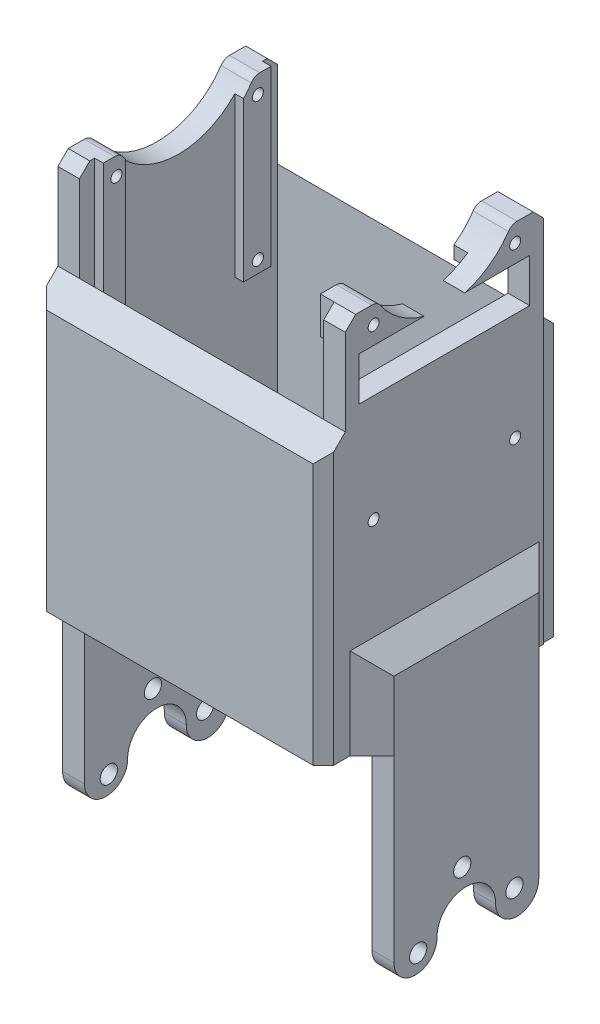
SolidWorks part; units mm, degrees
material "PLA"
ref_plane "Front Plane" through (0, 0, 0) normal (0, 0, 1) x (1, 0, 0)
ref_plane "Top Plane" through (0, 0, 0) normal (0, 1, 0) x (1, 0, 0)
ref_plane "Right Plane" through (0, 0, 0) normal (1, 0, 0) x (0, 0, -1)
sketch "Sketch1" plane through (0, 0, 0) normal (0, 0, 1) x (1, 0, 0)
  line L0 (0, 0) -> (35.4, 0)
  line L1 (35.4, 0) -> (35.4, 51.875)
  line L2 (0, 0) -> (-3.125, 0) construction
  line L3 (35.4, 0) -> (38.525, 0) construction
  line L4 (-3.125, -3.125) -> (38.525, -3.125)
  line L5 (38.525, -3.125) -> (38.525, 51.875)
  line L6 (-3.125, -3.125) -> (-3.125, 51.875)
  line L7 (0, 0) -> (0, 51.875)
  line L8 (0, 51.875) -> (-3.125, 51.875)
  line L9 (35.4, 51.875) -> (38.525, 51.875)
  dimension "D1" = 35.4
  dimension "D2" = 3.125
  dimension "D3" = 3.125
  dimension "D4" = 3.125
  dimension "D5" = 55
  dimension "D6" = 55
extrude "Boss-Extrude1" add sketch "Sketch1" along normal blind 28.72
sketch "Sketch2" plane through (38.525, 0, 0) normal (1, 0, 0) x (0, 0, -1)
  line L0 (-28.72, 46.285) -> (0, 46.285) construction
  line L1 (-28.72, -3.125) -> (-28.72, 51.875) construction
  line L2 (0, -3.125) -> (0, 51.875) construction
  line L3 (-28.72, 51.875) -> (0, 51.875) construction
  line L4 (-14.36, 46.285) -> (-14.36, 57.485) construction
  circle A0 centre (-14.36, 57.485) radius 11.2
  dimension "D1" = 5.59
  dimension "D2" = 11.2
extrude "Cut-Extrude1" cut sketch "Sketch2" against normal through all
fillet "Fillet2" radius 1.5 4 edges at (-1.5625, 51.875, 24.0537) (-1.5625, 51.875, 4.6663) (36.9625, 51.875, 4.6663) (36.9625, 51.875, 24.0537)
sketch "Sketch3" plane through (0, 0, 0) normal (0, 0, -1) x (-1, 0, 0)
  line L1 (-38.325, 37.875) -> (3.125, 37.875)
  line L2 (-38.325, 37.875) -> (-38.325, -3.125)
  line L3 (-38.325, -3.125) -> (3.125, -3.125)
  line L4 (3.125, 37.875) -> (3.125, -3.125)
extrude "Boss-Extrude2" add sketch "Sketch3" along normal blind 3.175
sketch "Sketch4" plane through (0, 0, 28.72) normal (0, 0, 1) x (1, 0, 0)
  line L1 (-3.125, 37.875) -> (38.525, 37.875)
  line L2 (-3.125, 37.875) -> (-3.125, -3.125)
  line L3 (-3.125, -3.125) -> (38.525, -3.125)
  line L4 (38.525, 37.875) -> (38.525, -3.125)
extrude "Boss-Extrude3" add sketch "Sketch4" along normal blind 3.175
chamfer "Chamfer1" distance 3.175 angle 45 2 edges at (17.6, 37.875, -3.175) (17.7, 37.875, 31.895)
chamfer "Chamfer2" distance 1.5 angle 45 4 edges at (-1.5625, 51.875, 0) (36.9625, 51.875, 0) (-1.5625, 51.875, 28.72) (36.9625, 51.875, 28.72)
chamfer "Chamfer3" distance 1.5 angle 45 4 edges at (-3.125, 15.7875, -3.175) (38.325, 15.7875, -3.175) (38.525, 15.7875, 31.895) (-3.125, 15.7875, 31.895)
sketch "Sketch5" plane through (0, 0, 0) normal (1, 0, 0) x (0, 0, -1)
  line L0 (-3.8368, 51.875) -> (-1.5, 51.875) construction
  line L2 (-2.2006, 51.875) -> (-2.2006, 26.7908)
  line L3 (-2.2006, 26.7908) -> (-6.2006, 26.7908)
  line L4 (-6.2006, 49.8127) -> (-6.2006, 26.7908)
  line L6 (-26.5194, 51.875) -> (-26.5194, 26.7908)
  line L7 (-26.5194, 26.7908) -> (-23.7797, 26.7908)
  line L8 (-23.7797, 51.4262) -> (-23.7797, 51.391)
  line L9 (-27.22, 51.875) -> (-24.8832, 51.875) construction
  line L10 (-3.8368, 51.875) -> (-2.2006, 51.875)
  line L11 (-26.5194, 51.875) -> (-24.8832, 51.875)
  line L12 (-23.7797, 26.7908) -> (-23.2826, 26.7908)
  line L13 (-23.2826, 26.7908) -> (-23.2826, 50.7154)
  circle A0 centre (-24.61, 49.2608) radius 0.8
  circle A1 centre (-24.61, 28.5608) radius 0.8
  circle A2 centre (-4.11, 28.5608) radius 0.8
  circle A3 centre (-4.11, 49.2608) radius 0.8
  arc A4 (-3.8368, 51.875) -> (-5.0797, 51.2148) centre (-3.8368, 50.375) ccw construction
  arc A5 (-23.6403, 51.2148) -> (-5.0797, 51.2148) centre (-14.36, 57.485) ccw construction
  arc A6 (-23.6403, 51.2148) -> (-24.8832, 51.875) centre (-24.8832, 50.375) ccw construction
  arc A7 (-3.8368, 51.875) -> (-5.0797, 51.2148) centre (-3.8368, 50.375) ccw
  arc A8 (-23.6403, 51.2148) -> (-23.7797, 51.4262) centre (-14.36, 57.485) ccw
  arc A9 (-23.6403, 51.2148) -> (-24.8832, 51.875) centre (-24.8832, 50.375) ccw
  arc A10 (-6.2006, 49.8127) -> (-5.0797, 51.2148) centre (-14.36, 57.485) ccw
  line M8 (-1.5, 51.875) -> (-3.8368, 51.875)
  arc M9 (-3.8368, 51.875) -> (-5.0797, 51.2148) centre (-3.8368, 50.375) ccw
  arc M10 (-5.0797, 51.2148) -> (-23.6403, 51.2148) centre (-14.36, 57.485) cw
  arc M11 (-23.6403, 51.2148) -> (-24.8832, 51.875) centre (-24.8832, 50.375) ccw
  line M12 (-24.8832, 51.875) -> (-27.22, 51.875)
extrude "Boss-Extrude4" add sketch "Sketch5" along normal blind 1.25 contours L4 L3 L2 A3 A2 M10 M8 M9 | L8 L6 L7 A1 A0 M11 M12 region at (0, 39.1233, 4.1775) region at (0, 39.2642, 24.9256)
sketch "Sketch6" plane through (0, 0, 0) normal (1, 0, 0) x (0, 0, -1)
  circle A0 centre (-24.61, 49.2608) radius 0.8
  circle A1 centre (-24.61, 28.5608) radius 0.8
  circle A2 centre (-4.11, 28.5608) radius 0.8
  circle A3 centre (-4.11, 49.2608) radius 0.8
extrude "Cut-Extrude2" cut sketch "Sketch6" against normal up to next
sketch "Sketch7" plane through (0, -3.125, 0) normal (0, -1, 0) x (1, 0, 0)
  line L0 (11.7, 22.36) -> (23.7, 22.36) construction
  line L1 (23.7, 22.36) -> (23.7, 6.36) construction
  line L2 (23.7, 6.36) -> (11.7, 6.36) construction
  line L3 (11.7, 6.36) -> (11.7, 22.36) construction
  line L6 (-3.125, 30.395) -> (-3.125, -1.675) construction
  line L7 (-1.625, 31.895) -> (37.025, 31.895) construction
  circle A0 centre (11.7, 22.36) radius 1.35
  circle A1 centre (23.7, 22.36) radius 1.35
  circle A2 centre (23.7, 6.36) radius 1.35
  circle A3 centre (11.7, 6.36) radius 1.35
  dimension "D1" = 2.7
  dimension "D2" = 2.7
  dimension "D3" = 2.7
  dimension "D4" = 2.7
  dimension "D5" = 14.825
  dimension "D6" = 9.535
extrude "Cut-Extrude3" cut sketch "Sketch7" against normal up to next
sketch "Sketch8" plane through (35.4, 0, 0) normal (-1, 0, 0) x (0, 0, 1)
  line L0 (7.86, 48.7133) -> (7.86, 45.9108) construction
  line L1 (1.5, 51.875) -> (5.0709, 51.875)
  line L2 (1.5, 51.875) -> (1.5, 46.5164)
  line L3 (1.5, 46.5164) -> (7.86, 46.5164)
  line L4 (7.86, 48.7133) -> (7.86, 46.5164)
  line L5 (20.86, 45.9108) -> (20.86, 48.7133) construction
  line L6 (20.86, 46.5164) -> (27.22, 46.5164)
  line L7 (20.86, 46.5164) -> (20.86, 48.7133)
  line L8 (23.6491, 51.875) -> (27.22, 51.875)
  line L9 (27.22, 46.5164) -> (27.22, 51.875)
  line L10 (28.72, 0) -> (28.72, 37.875) construction
  line L11 (28.72, 27.0608) -> (0, 27.0608)
  line L12 (28.72, 27.0608) -> (28.72, 22.5608)
  line L13 (28.72, 22.5608) -> (0, 22.5608)
  line L14 (0, 27.0608) -> (0, 22.5608)
  circle A0 centre (24.61, 49.2608) radius 0.8
  circle A1 centre (4.11, 49.2608) radius 0.8
  circle A2 centre (4.11, 24.8108) radius 0.8
  circle A3 centre (24.61, 24.735) radius 0.8758
  arc A4 (5.0077, 51.9796) -> (7.7768, 48.8846) centre (14.36, 57.5608) ccw construction
  arc A5 (5.0709, 51.875) -> (7.7768, 48.8846) centre (14.36, 57.5608) ccw
  arc A6 (20.9432, 48.8846) -> (23.7123, 51.9796) centre (14.36, 57.5608) ccw construction
  arc A7 (20.9432, 48.8846) -> (23.6491, 51.875) centre (14.36, 57.5608) ccw
  spline S0 degree 3 poles (-1990.0282, 140.523) (-63.2874, 38.9164) (7.1505, 51.8916) (8.5344, 45.7425) (-54.2619, 48.1267) (797.0615, -1788.4088) knots -94.086847 -94.086847 -94.086847 -94.086847 0.333333 0.666667 91.791331 91.791331 91.791331 91.791331 weights 1 1 1 1 1 1 only from (7.8374, 48.8108) to (7.86, 48.7133) construction
  spline S1 degree 3 poles (-490.8158, 1985.2839) (-30.2177, -10.261) (5.7924, 51.2853) (9.6673, 46.6143) (-37.1403, 7.4582) (460.9115, -1898.6662) knots -96.396237 -96.396237 -96.396237 -96.396237 0.333333 0.666667 89.616596 89.616596 89.616596 89.616596 weights 1 1 1 1 1 1 only from (7.7768, 48.8846) to (7.8374, 48.8108) construction
  spline S2 degree 3 poles (7.8374, 48.8108) (7.8425, 48.8003) (7.851, 48.7791) (7.8584, 48.746) (7.86, 48.7242) (7.86, 48.7133) knots 0 0 0 0 0.333333 0.666667 1 1 1 1 weights 1 1 1 1 1 1
  spline S3 degree 3 poles (7.7768, 48.8846) (7.785, 48.8784) (7.8005, 48.8647) (7.8213, 48.8396) (7.8325, 48.8208) (7.8374, 48.8108) knots 0 0 0 0 0.333333 0.666667 1 1 1 1 weights 1 1 1 1 1 1
  spline S4 degree 3 poles (356.7329, 2019.8863) (65.3071, 28.7044) (19.6993, 46.3936) (21.999, 51.095) (61.1419, 27.6757) (-1071.4379, -1626.044) knots -39.976297 -39.976297 -39.976297 -39.976297 0.341381 0.67758 38.768425 38.768425 38.768425 38.768425 weights 1 1 1 1 1 1 only from (20.86, 48.7133) to (20.9432, 48.8846) construction
  spline S5 degree 3 poles (20.86, 48.7133) (20.86, 48.7357) (20.8668, 48.7804) (20.896, 48.8401) (20.9264, 48.8718) (20.9432, 48.8846) knots 0 0 0 0 0.341381 0.67758 1 1 1 1 weights 1 1 1 1 1 1
  point P42 (0, 24.8108)
  line M9 (0, 37.875) -> (0, 0)
  line M11 (28.72, 0) -> (28.72, 37.875)
  line M14 (27.22, 51.875) -> (24.8832, 51.875)
  arc M15 (24.8832, 51.875) -> (23.6403, 51.2148) centre (24.8832, 50.375) ccw
  arc M16 (23.6403, 51.2148) -> (5.0797, 51.2148) centre (14.36, 57.485) cw
  arc M17 (5.0797, 51.2148) -> (3.8368, 51.875) centre (3.8368, 50.375) ccw
  line M18 (3.8368, 51.875) -> (1.5, 51.875)
  dimension "D1" = 4.5
extrude "Boss-Extrude5" add sketch "Sketch8" along normal blind 2 contours L6 L9 L7 A0 M14 M15 M16 | L4 L2 L3 A1 M16 M17 M18 | L13 L11 A3 A2 M11 M9 region at (35.4, 49.6068, 22.4374) region at (35.4, 51.7918, 2.6684) region at (35.4, 24.8122, 14.3273)
sketch "Sketch9" plane through (35.4, 0, 0) normal (-1, 0, 0) x (0, 0, 1)
  line L0 (24.61, 50.0607) -> (24.61, 48.4608) construction
  line L1 (4.11, 50.0607) -> (4.11, 48.4608) construction
  line L2 (4.11, 25.6107) -> (4.11, 24.0108) construction
  line L3 (24.61, 25.6107) -> (24.61, 24.0108) construction
  line L4 (26.72, 24.4506) -> (26.72, 51.0993) construction
  line L5 (26.72, 46.6769) -> (2, 46.6769)
  line L6 (26.72, 46.6769) -> (26.72, 40.3691)
  line L7 (26.72, 40.3691) -> (2, 40.3691)
  line L8 (2, 46.6769) -> (2, 40.3691)
  line L9 (2, 51.0993) -> (2, 24.4506) construction
  circle A0 centre (24.61, 24.8107) radius 0.8
  circle A1 centre (4.11, 24.8107) radius 0.8
  circle A2 centre (4.11, 49.2607) radius 0.8
  circle A3 centre (24.61, 49.2607) radius 0.8
extrude "Cut-Extrude4" cut sketch "Sketch9" against normal up to next
sketch "Sketch10" plane through (-3.125, 0, 0) normal (-1, 0, 0) x (0, 0, 1)
  line L0 (3.86, -9.6264) -> (3.86, 3.5377) construction
  line L1 (3.86, -29.0691) -> (3.86, -5.125) construction
  line L2 (24.86, -9.6264) -> (24.86, 3.5377) construction
  line L3 (24.86, -29.0691) -> (24.86, -5.125) construction
  line L4 (30.395, -3.125) -> (-1.675, -3.125) construction
  line L5 (3.86, 6.875) -> (24.86, 6.875)
  line L6 (3.86, 6.875) -> (3.86, -29.0691)
  line L8 (24.86, 6.875) -> (24.86, -29.0691)
  spline S0 degree 3 poles (6.1384, -28.3409) (6.0777, -29.0707) (6.5507, -29.6296) (7.2805, -29.6903) knots 0 0 0 0 1 1 1 1 weights 1 0.804738 0.804738 1 construction
  spline S1 degree 3 poles (6.1384, -28.3409) (6.2469, -27.0371) (7.493, -26.6384) (8.3382, -27.637) (9.1835, -28.6357) (8.5843, -29.7988) (7.2805, -29.6903) knots 0 0 0 0 0.5 0.5 0.5 1 1 1 1 weights 1 0.588456 0.588456 1 0.588456 0.588456 1 construction
  spline S2 degree 3 poles (15.0441, -20.8034) (14.3143, -20.7427) (13.7554, -21.2157) (13.6947, -21.9455) knots 0 0 0 0 1 1 1 1 weights 1 0.804738 0.804738 1 construction
  spline S3 degree 3 poles (15.0441, -20.8034) (16.3479, -20.9119) (16.7466, -22.158) (15.748, -23.0032) (14.7493, -23.8485) (13.5862, -23.2493) (13.6947, -21.9455) knots 0 0 0 0 0.5 0.5 0.5 1 1 1 1 weights 1 0.588456 0.588456 1 0.588456 0.588456 1 construction
  spline S4 degree 3 poles (22.5816, -29.7091) (22.6423, -28.9793) (22.1693, -28.4204) (21.4395, -28.3597) knots 0 0 0 0 1 1 1 1 weights 1 0.804738 0.804738 1 construction
  spline S5 degree 3 poles (22.5816, -29.7091) (22.4731, -31.0129) (21.227, -31.4116) (20.3818, -30.413) (19.5365, -29.4143) (20.1357, -28.2512) (21.4395, -28.3597) knots 0 0 0 0 0.5 0.5 0.5 1 1 1 1 weights 1 0.588456 0.588456 1 0.588456 0.588456 1 construction
  spline S6 degree 3 poles (18.6098, -29.0691) (18.6098, -35.3193) (24.86, -35.3193) (24.86, -29.0691) knots 0 0 0 0 1 1 1 1 weights 1 0.333333 0.333333 1 construction
  spline S7 degree 3 poles (10.1102, -29.0691) (10.0842, -26.5591) (11.8499, -24.775) (14.36, -24.775) (16.8701, -24.775) (18.6358, -26.5591) (18.6098, -29.0691) knots 0 0 0 0 0.5 0.5 0.5 1 1 1 1 weights 1 0.802287 0.802287 1 0.802287 0.802287 1 construction
  spline S8 degree 3 poles (3.86, -29.0691) (3.86, -30.8997) (5.1545, -32.1942) (6.9851, -32.1942) (8.8158, -32.1942) (10.1102, -30.8997) (10.1102, -29.0691) knots 0 0 0 0 0.5 0.5 0.5 1 1 1 1 weights 1 0.804738 0.804738 1 0.804738 0.804738 1 construction
  spline S9 degree 3 poles (6.1384, -28.3409) (6.0777, -29.0707) (6.5507, -29.6296) (7.2805, -29.6903) knots 0 0 0 0 1 1 1 1 weights 1 0.804738 0.804738 1
  spline S10 degree 3 poles (6.1384, -28.3409) (6.2469, -27.0371) (7.493, -26.6384) (8.3382, -27.637) (9.1835, -28.6357) (8.5843, -29.7988) (7.2805, -29.6903) knots 0 0 0 0 0.5 0.5 0.5 1 1 1 1 weights 1 0.588456 0.588456 1 0.588456 0.588456 1
  spline S11 degree 3 poles (15.0441, -20.8034) (14.3143, -20.7427) (13.7554, -21.2157) (13.6947, -21.9455) knots 0 0 0 0 1 1 1 1 weights 1 0.804738 0.804738 1
  spline S12 degree 3 poles (15.0441, -20.8034) (16.3479, -20.9119) (16.7466, -22.158) (15.748, -23.0032) (14.7493, -23.8485) (13.5862, -23.2493) (13.6947, -21.9455) knots 0 0 0 0 0.5 0.5 0.5 1 1 1 1 weights 1 0.588456 0.588456 1 0.588456 0.588456 1
  spline S13 degree 3 poles (22.5816, -29.7091) (22.6423, -28.9793) (22.1693, -28.4204) (21.4395, -28.3597) knots 0 0 0 0 1 1 1 1 weights 1 0.804738 0.804738 1
  spline S14 degree 3 poles (22.5816, -29.7091) (22.4731, -31.0129) (21.227, -31.4116) (20.3818, -30.413) (19.5365, -29.4143) (20.1357, -28.2512) (21.4395, -28.3597) knots 0 0 0 0 0.5 0.5 0.5 1 1 1 1 weights 1 0.588456 0.588456 1 0.588456 0.588456 1
  spline S15 degree 3 poles (18.6098, -29.0691) (18.6098, -35.3193) (24.86, -35.3193) (24.86, -29.0691) knots 0 0 0 0 1 1 1 1 weights 1 0.333333 0.333333 1
  spline S16 degree 3 poles (10.1102, -29.0691) (10.0842, -26.5591) (11.8499, -24.775) (14.36, -24.775) (16.8701, -24.775) (18.6358, -26.5591) (18.6098, -29.0691) knots 0 0 0 0 0.5 0.5 0.5 1 1 1 1 weights 1 0.802287 0.802287 1 0.802287 0.802287 1
  spline S17 degree 3 poles (3.86, -29.0691) (3.86, -30.8997) (5.1545, -32.1942) (6.9851, -32.1942) (8.8158, -32.1942) (10.1102, -30.8997) (10.1102, -29.0691) knots 0 0 0 0 0.5 0.5 0.5 1 1 1 1 weights 1 0.804738 0.804738 1 0.804738 0.804738 1
  dimension "D1" = 10
extrude "Boss-Extrude6" add sketch "Sketch10" along normal blind 3.175
chamfer "Chamfer8" distance 3.175 angle 45 3 edges at (-3.125, 1.875, 3.86) (-3.125, 6.875, 14.36) (-3.125, 1.875, 24.86)
ref_plane "Plane1" through (17.7, 0, 0) normal (1, 0, 0) x (0, 0, -1)
mirror "Mirror2" about plane through (17.7, 0, 0) normal (1, 0, 0) of "Boss-Extrude6"
chamfer "Chamfer9" distance 3.175 angle 45 3 edges at (38.525, 1.875, 24.86) (38.525, 6.875, 14.36) (38.525, 1.875, 3.86)
